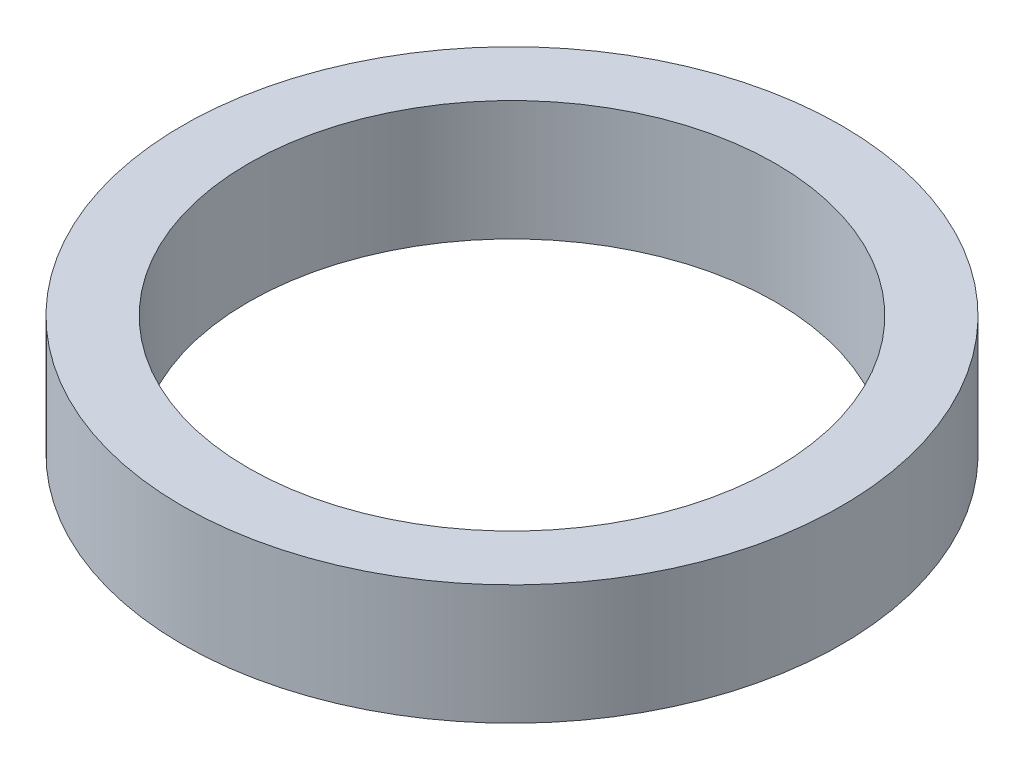
SolidWorks part; units mm, degrees
ref_plane "Front Plane" through (0, 0, 0) normal (0, 0, 1) x (1, 0, 0)
ref_plane "Top Plane" through (0, 0, 0) normal (0, 1, 0) x (1, 0, 0)
ref_plane "Right Plane" through (0, 0, 0) normal (1, 0, 0) x (0, 0, -1)
sketch "Sketch1" plane through (0, 0, 0) normal (0, 1, 0) x (1, 0, 0)
  circle A0 centre (0, 0) radius 55
  circle A1 centre (0, 0) radius 44
  dimension "D1" = 110
  dimension "D2" = 88
extrude "Boss-Extrude1" add sketch "Sketch1" along normal blind 10 and the other way blind 10
